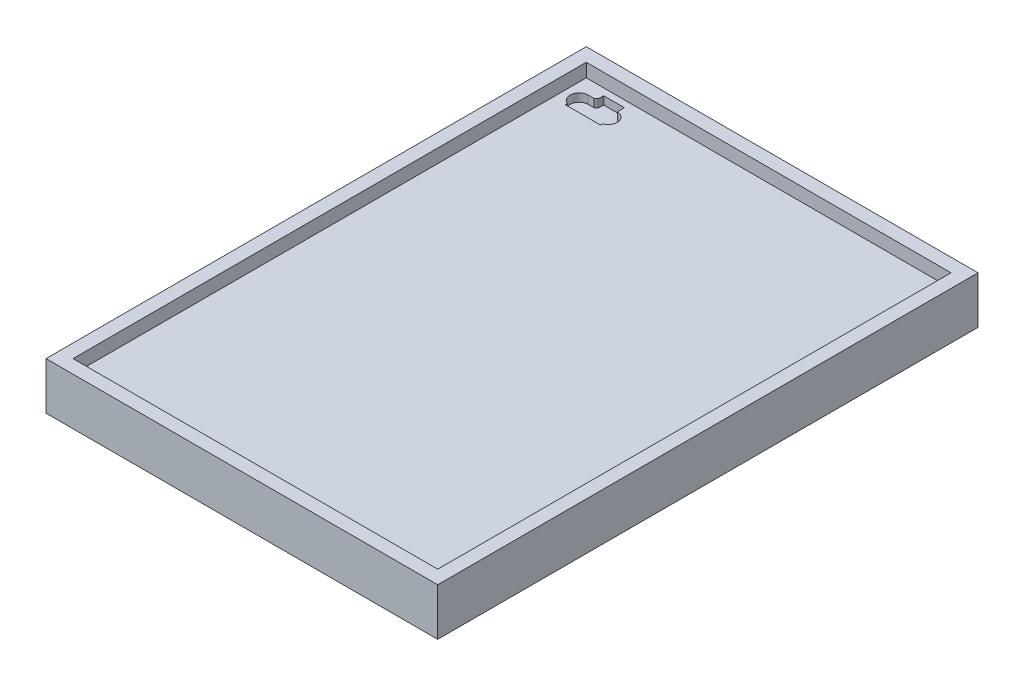
SolidWorks part; units mm, degrees
ref_plane "Front Plane" through (0, 0, 0) normal (0, 0, 1) x (1, 0, 0)
ref_plane "Top Plane" through (0, 0, 0) normal (0, 1, 0) x (1, 0, 0)
ref_plane "Right Plane" through (0, 0, 0) normal (1, 0, 0) x (0, 0, -1)
sketch "Sketch1" plane through (0, 0, 0) normal (0, 1, 0) x (1, 0, 0)
  line L1 (-145, 200) -> (145, 200)
  line L2 (-145, 200) -> (-145, -200)
  line L3 (-145, -200) -> (145, -200)
  line L4 (145, 200) -> (145, -200)
  line L5 (-145, 200) -> (145, -200) construction
  line L6 (-145, -200) -> (145, 200) construction
  point P0 (0, 0)
  dimension "D1" = 290
  dimension "D2" = 400
extrude "Boss-Extrude1" add sketch "Sketch1" along normal blind 35
sketch "Sketch2" plane through (0, 35, 0) normal (0, 1, 0) x (1, 0, 0)
  line L0 (145, -200) -> (145, 200) construction
  line L1 (-145, -200) -> (145, -200) construction
  line L2 (-145, 200) -> (-145, -200) construction
  line L3 (145, 200) -> (-145, 200) construction
  line L4 (145, -200) -> (145, 200)
  line L5 (-145, -200) -> (145, -200)
  line L6 (-145, 200) -> (-145, -200)
  line L7 (145, 200) -> (-145, 200)
  line L8 (135, -190) -> (135, 190)
  line L9 (135, 190) -> (-135, 190)
  line L10 (-135, 190) -> (-135, -190)
  line L11 (-135, -190) -> (135, -190)
  dimension "D1" = 10
extrude "Cut-Extrude2" cut sketch "Sketch2" against normal blind 10 contours L8 L9 L10 L11
sketch "Sketch3" plane through (0, 25, 0) normal (0, 1, 0) x (1, 0, 0)
  line L0 (0, 211.8692) -> (0, -222.8207) construction
  line L1 (-219.8723, 0) -> (201.339, 0) construction
  line L2 (135, 190) -> (-135, 190) construction
  line L3 (135, 190) -> (-135, 190) construction
  line L4 (135, 185) -> (-135, 185) construction
  line L5 (135, 165) -> (-135, 165) construction
  line L6 (-135, 190) -> (-135, -190) construction
  line L7 (-135, 190) -> (-135, -190) construction
  line L8 (-130, 190) -> (-130, -190) construction
  line L9 (-95, 190) -> (-95, -190) construction
  line L10 (-112.5, 190) -> (-112.5, -190) construction
  line L11 (-117.13, 185) -> (-101.75, 185)
  line L13 (-139, 190) -> (-139, -190)
  line L15 (-101.75, 199.739) -> (-101.75, 174.9169) construction
  line L16 (-99.4062, 166.62) -> (-99.4062, 165)
  line L17 (-101.75, 179.7) -> (-101.75, 185)
  line L18 (-125.5938, 165) -> (-99.4062, 165)
  line L19 (-125.5938, 166.62) -> (-125.5938, 165)
  line L20 (-123.25, 179.7) -> (-118.8793, 179.7)
  line L25 (-117.13, 185) -> (-117.13, 181.5)
  line L26 (-117.13, 181.5) -> (-118.8793, 179.7)
  line L61 (-117.13, 185) -> (-72.13, 185) construction
  arc A1 (-123.25, 179.7) -> (-125.5938, 166.62) centre (-123.25, 172.95) ccw
  arc A2 (-101.75, 179.7) -> (-99.4062, 166.62) centre (-101.75, 172.95) cw
  point P19 (0, 0)
  point P20 (135, 172.25)
  point P21 (-135, 173.09)
  point P24 (-126.7855, 190)
  point P25 (115.6811, -99.309)
  point P29 (0, 0)
  point P40 (-112.5, 165)
  dimension "D11" = 2.51
  dimension "D9" = 13.5
  dimension "D12" = 3.5
  dimension "D6" = 5.3
  dimension "D7" = 1.62
  dimension "D13" = 45
  dimension "D3" = 5
  dimension "D4" = 35
  dimension "D5" = 17.5
  dimension "D8" = 26.5
extrude "Cut-Extrude3" cut sketch "Sketch3" against normal blind 6 contours A2 L17 L11 L25 L26 L20 A1 L19 L18 L16 region at (-112.0602, 25, -173.939)
fillet "Fillet2" radius 2 1 edges at (-117.13, 22, -181.5)
fillet "Fillet4" radius 0.5 1 edges at (-125.5938, 22, -166.62)
fillet "Fillet5" radius 0.5 1 edges at (-99.4062, 22, -166.62)
fillet "Fillet6" radius 0.5 1 edges at (-101.75, 22, -179.7)
fillet "Fillet7" radius 0.5 1 edges at (-101.75, 22, -185)
fillet "Fillet8" radius 0.5 1 edges at (-117.13, 22, -185)
fillet "Fillet9" radius 0.5 2 edges at (-125.5938, 22, -165) (-99.4062, 22, -165)
